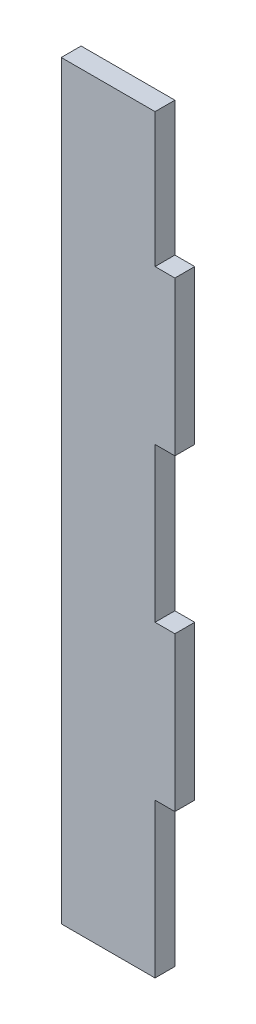
SolidWorks part; units mm, degrees
ref_plane "Front Plane" through (0, 0, 0) normal (0, 0, 1) x (1, 0, 0)
ref_plane "Top Plane" through (0, 0, 0) normal (0, 1, 0) x (1, 0, 0)
ref_plane "Right Plane" through (0, 0, 0) normal (1, 0, 0) x (0, 0, -1)
sketch "Sketch1" plane through (0, 0, 0) normal (0, 0, 1) x (1, 0, 0)
  line L1 (0, 0) -> (15, 0)
  line L2 (0, 0) -> (0, 120)
  line L13 (0, 120) -> (15, 120)
  line L24 (15, 120) -> (15, 98.54)
  line L25 (15, 98.54) -> (18.175, 98.54)
  line L26 (18.175, 98.54) -> (18.175, 73.905)
  line L27 (18.175, 73.905) -> (15, 73.905)
  line L28 (15, 73.905) -> (15, 49.27)
  line L29 (15, 49.27) -> (18.175, 49.27)
  line L30 (18.175, 49.27) -> (18.175, 24.635)
  line L31 (18.175, 24.635) -> (15, 24.635)
  line L32 (15, 24.635) -> (15, 0)
  dimension "D1" = 120
  dimension "D2" = 21.46
  dimension "D3" = 3.175
extrude "Boss-Extrude1" add sketch "Sketch1" along normal blind 3.175
